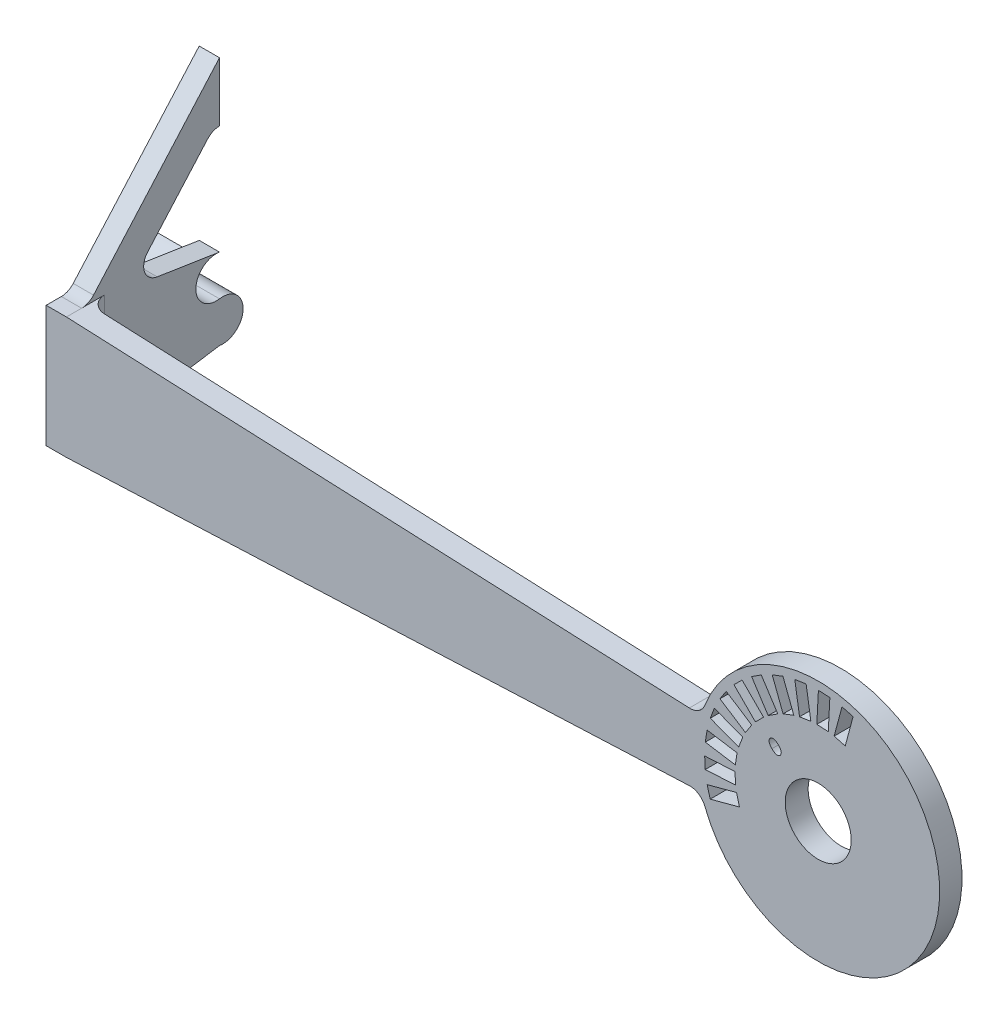
SolidWorks part; units mm, degrees
ref_plane "Front Plane" through (0, 0, 0) normal (0, 0, 1) x (1, 0, 0)
ref_plane "Top Plane" through (0, 0, 0) normal (0, 1, 0) x (1, 0, 0)
ref_plane "Right Plane" through (0, 0, 0) normal (1, 0, 0) x (0, 0, -1)
sketch "Sketch1" plane through (0, 0, 0) normal (0, 0, 1) x (1, 0, 0)
  circle A1 centre (27.25, 7.75) radius 5 construction
  circle A2 centre (27.25, 7.75) radius 9.525
  circle A3 centre (27.25, 7.75) radius 5.175
  dimension "D1" = 19.05
  dimension "D5" = 10
  dimension "D3" = 7.75
  dimension "D4" = 27.25
  dimension "D2" = 0.175
extrude "Boss-Extrude1" add sketch "Sketch1" against normal blind 3.6
sketch "Sketch2" plane through (0, 0, 0) normal (0, 0, 1) x (1, 0, 0)
  line L0 (18.995, 12.5019) -> (-90.625, 17.288)
  line L1 (18.995, 2.9981) -> (-90.625, -1.788)
  line L2 (18.995, 12.5019) -> (18.995, 2.9981)
  line L3 (-90.625, 17.288) -> (-90.625, -1.788)
  circle A0 centre (27.25, 7.75) radius 9.525 construction
  circle A1 centre (27.25, 7.75) radius 5.175 construction
  dimension "D1" = 87.5
  dimension "D2" = 87.5
  dimension "D3" = 8.255
  dimension "D4" = 109.62
extrude "Boss-Extrude2" add sketch "Sketch2" against normal blind 3.5
sketch "Sketch3" plane through (0, 0, 0) normal (0, 0, 1) x (1, 0, 0)
  circle A0 centre (27.25, 7.75) radius 19.05
  circle A1 centre (27.25, 7.75) radius 5.175 construction
  circle A2 centre (27.25, 7.75) radius 5.175
  dimension "D1" = 38.1
extrude "Boss-Extrude3" add sketch "Sketch3" against normal blind 3.5
sketch "Sketch4" plane through (0, 0, 0) normal (0, 0, 1) x (1, 0, 0)
  line L2 (27.25, 7.75) -> (20.4231, 25.5347) construction
  line L3 (27.25, 7.75) -> (24.2699, 26.5655) construction
  line L4 (27.25, 7.75) -> (28.247, 26.7739) construction
  line L5 (27.25, 7.75) -> (32.1805, 26.1509) construction
  line L6 (27.25, 7.75) -> (29.4192, 5.5808) construction
  line L12 (27.25, 7.75) -> (8.8491, 2.8195) construction
  line L13 (27.25, 7.75) -> (8.2261, 6.753) construction
  line L14 (27.25, 7.75) -> (8.4345, 10.7301) construction
  line L15 (27.25, 7.75) -> (9.4653, 14.5769) construction
  line L16 (27.25, 7.75) -> (11.2733, 18.1254) construction
  line L17 (13.7796, 21.2204) -> (11.2733, 18.1254) construction
  line L19 (13.7796, 21.2204) -> (16.8746, 23.7267) construction
  line L20 (16.8746, 23.7267) -> (20.4231, 25.5347) construction
  line L21 (20.4231, 25.5347) -> (24.2699, 26.5655) construction
  line L22 (24.2699, 26.5655) -> (28.247, 26.7739) construction
  line L23 (28.247, 26.7739) -> (32.1805, 26.1509) construction
  line L25 (8.2261, 6.753) -> (8.8491, 2.8195) construction
  line L26 (8.4345, 10.7301) -> (8.2261, 6.753) construction
  line L27 (9.4653, 14.5769) -> (8.4345, 10.7301) construction
  line L28 (11.2733, 18.1254) -> (9.4653, 14.5769) construction
  line L29 (19.4054, 18.1772) -> (16.8115, 22.1714)
  line L30 (17.4088, 16.3184) -> (18.6816, 17.5912)
  line L31 (17.4088, 16.3184) -> (14.0412, 19.686)
  line L32 (14.0412, 19.686) -> (15.314, 20.9588)
  line L33 (18.6816, 17.5912) -> (15.314, 20.9588)
  line L34 (14.6776, 20.3224) -> (18.0452, 16.9548) construction
  line L35 (15.725, 18.0022) -> (16.9978, 19.275) construction
  line L36 (19.4054, 18.1772) -> (20.915, 19.1576)
  line L37 (20.915, 19.1576) -> (18.3211, 23.1517)
  line L38 (16.8115, 22.1714) -> (18.3211, 23.1517)
  line L39 (21.7447, 19.5804) -> (20.038, 24.0265)
  line L40 (21.7447, 19.5804) -> (23.4252, 20.2254)
  line L41 (23.4252, 20.2254) -> (21.7184, 24.6716)
  line L42 (20.038, 24.0265) -> (21.7184, 24.6716)
  line L43 (24.3247, 20.4664) -> (23.5797, 25.1703)
  line L44 (24.3247, 20.4664) -> (26.1025, 20.748)
  line L45 (26.1025, 20.748) -> (25.3575, 25.4519)
  line L46 (23.5797, 25.1703) -> (25.3575, 25.4519)
  line L47 (27.0325, 20.7968) -> (27.2818, 25.5527)
  line L48 (27.0325, 20.7968) -> (28.83, 20.7026)
  line L49 (28.83, 20.7026) -> (29.0793, 25.4585)
  line L50 (27.2818, 25.5527) -> (29.0793, 25.4585)
  line L51 (29.7498, 20.5569) -> (30.9825, 25.1571)
  line L52 (29.7498, 20.5569) -> (31.4885, 20.091)
  line L53 (31.4885, 20.091) -> (32.7211, 24.6912)
  line L54 (30.9825, 25.1571) -> (32.7211, 24.6912)
  line L61 (15.8424, 14.085) -> (11.8483, 16.6789)
  line L62 (15.8424, 14.085) -> (16.8228, 15.5946)
  line L63 (16.8228, 15.5946) -> (12.8286, 18.1885)
  line L64 (11.8483, 16.6789) -> (12.8286, 18.1885)
  line L65 (14.7746, 11.5748) -> (10.3284, 13.2816)
  line L66 (14.7746, 11.5748) -> (15.4196, 13.2553)
  line L67 (15.4196, 13.2553) -> (10.9735, 14.962)
  line L68 (10.3284, 13.2816) -> (10.9735, 14.962)
  line L69 (14.252, 8.8975) -> (9.5481, 9.6425)
  line L70 (14.252, 8.8975) -> (14.5336, 10.6753)
  line L71 (14.5336, 10.6753) -> (9.8297, 11.4203)
  line L72 (9.5481, 9.6425) -> (9.8297, 11.4203)
  line L73 (14.2974, 6.17) -> (9.5415, 5.9207)
  line L74 (14.2974, 6.17) -> (14.2032, 7.9675)
  line L75 (14.2032, 7.9675) -> (9.4473, 7.7182)
  line L76 (9.5415, 5.9207) -> (9.4473, 7.7182)
  line L77 (14.909, 3.5115) -> (10.3088, 2.2789)
  line L78 (14.909, 3.5115) -> (14.4431, 5.2502)
  line L79 (14.4431, 5.2502) -> (9.8429, 4.0175)
  line L80 (10.3088, 2.2789) -> (9.8429, 4.0175)
  line L87 (15.2427, 2.6421) -> (10.9993, 0.48) [skipped]
  line L88 (16.0599, 1.0383) -> (15.2427, 2.6421) [skipped]
  line L89 (16.0599, 1.0383) -> (11.8165, -1.1239) [skipped]
  line L90 (11.8165, -1.1239) -> (10.9993, 0.48) [skipped]
  line L91 (33.9617, 18.9401) -> (36.1239, 23.1835) [skipped]
  line L92 (34.52, 24.0007) -> (36.1239, 23.1835) [skipped]
  line L93 (32.3579, 19.7573) -> (34.52, 24.0007) [skipped]
  line L94 (32.3579, 19.7573) -> (33.9617, 18.9401) [skipped]
  text T0 "\r\n0" font "Century Gothic" height in points 8
  point P23 (16.3614, 18.6386)
  dimension "D5" = 7
  dimension "D7" = 7
extrude "Cut-Extrude1" cut sketch "Sketch4" against normal through all
sketch "Sketch5" plane through (-90.625, 0, 0) normal (-1, 0, 0) x (0, 0, 1)
  line L0 (-24, 7.75) -> (0, 7.75) construction
  line L1 (0, 17.288) -> (0, -1.788) construction
  line L2 (-3.5, 17.275) -> (-3.5, -1.775) construction
  line L3 (0, 17.288) -> (-3.5, 17.288)
  line L4 (-3.5, 17.288) -> (-24, 14.1)
  line L5 (-24, 1.4) -> (-3.5, -1.788)
  line L6 (-3.5, -1.788) -> (0, -1.788)
  line L7 (0, -1.788) -> (0, 17.288)
  circle A0 centre (-24, 7.75) radius 6.35
  arc A1 (-24, 14.1) -> (-24, 7.75) centre (-23.5062, 10.925) cw
  arc A2 (-24, 7.75) -> (-24, 1.4) centre (-24.4938, 4.575) ccw
  dimension "D2" = 12.7
  dimension "D1" = 20.5
extrude "Boss-Extrude4" add sketch "Sketch5" along normal blind 3.175 contours A2 L5 L6 L7 L3 L4 A1
sketch "Sketch6" plane through (-93.8, 0, 0) normal (-1, 0, 0) x (0, 0, 1)
  circle A0 centre (-24, 7.75) radius 6.35
  arc A1 (-24, 7.75) -> (-24, 1.4) centre (-24.4938, 4.575) ccw construction
  arc A2 (-24, 7.75) -> (-24, 14.1) centre (-23.5062, 10.925) ccw construction
  arc A3 (-24, 7.75) -> (-24, 1.4) centre (-24.4938, 4.575) ccw
  arc A4 (-24, 7.75) -> (-24, 14.1) centre (-23.5062, 10.925) ccw
  arc M2 (-24, 14.1) -> (-24, 7.75) centre (-23.5062, 10.925) cw
  arc M3 (-24, 7.75) -> (-24, 1.4) centre (-24.4938, 4.575) ccw
  dimension "D1" = 12.7
extrude "Boss-Extrude5" add sketch "Sketch6" along normal blind 6.35 contours A0 M3 M2
sketch "Sketch7" [suppressed] plane through (0, 0, 0) normal (0, 0, 1) x (1, 0, 0)
  line L0 (27.25, 7.75) -> (36.775, 7.75) construction
  line L1 (33.7154, 7.0147) -> (33.4555, 5.792)
  line L2 (34.362, 8.375) -> (35.124, 8.375)
  line L3 (33.727, 7.74) -> (33.727, 7.76)
  line L4 (34.362, 7.125) -> (35.124, 7.125)
  line L5 (35.759, 7.74) -> (35.759, 7.76)
  line L6 (34.743, 7.125) -> (34.743, 8.375) construction
  line L7 (33.727, 7.75) -> (35.759, 7.75) construction
  line L8 (33.7154, 7.0147) -> (35.703, 6.5922)
  line L9 (35.703, 6.5922) -> (35.4431, 5.3695)
  line L10 (33.4555, 5.792) -> (35.4431, 5.3695)
  line L11 (27.25, 7.75) -> (36.5669, 5.7696) construction
  line L12 (33.4212, 5.6865) -> (32.9128, 4.5446)
  line L13 (33.4212, 5.6865) -> (35.2776, 4.86)
  line L14 (35.2776, 4.86) -> (34.7691, 3.7181)
  line L15 (32.9128, 4.5446) -> (34.7691, 3.7181)
  line L16 (27.25, 7.75) -> (35.9515, 3.8758) construction
  line L17 (32.8574, 4.4486) -> (32.1226, 3.4373)
  line L18 (32.8574, 4.4486) -> (34.5013, 3.2542)
  line L19 (34.5013, 3.2542) -> (33.7666, 2.2429)
  line L20 (32.1226, 3.4373) -> (33.7666, 2.2429)
  line L21 (27.25, 7.75) -> (34.9559, 2.1513) construction
  line L22 (32.0484, 3.3549) -> (31.1195, 2.5184)
  line L23 (32.0484, 3.3549) -> (33.4081, 1.8448)
  line L24 (33.4081, 1.8448) -> (32.4792, 1.0084)
  line L25 (31.1195, 2.5184) -> (32.4792, 1.0084)
  line L26 (27.25, 7.75) -> (33.6235, 0.6715) construction
  line L27 (31.0298, 2.4533) -> (29.9472, 1.8283)
  line L28 (31.0298, 2.4533) -> (32.0458, 0.6935)
  line L29 (32.0458, 0.6935) -> (30.9632, 0.0685)
  line L30 (29.9472, 1.8283) -> (30.9632, 0.0685)
  line L31 (27.25, 7.75) -> (32.0125, -0.4989) construction
  line L32 (29.8459, 1.7831) -> (28.6571, 1.3969)
  line L33 (29.8459, 1.7831) -> (30.4738, -0.1494)
  line L34 (30.4738, -0.1494) -> (29.285, -0.5357)
  line L35 (28.6571, 1.3969) -> (29.285, -0.5357)
  line L36 (27.25, 7.75) -> (30.1934, -1.3088) construction
  line L37 (27.25, 7.75) -> (33.727, 7.125) construction
  line L38 (27.25, 7.75) -> (33.4555, 5.792) construction
  line L39 (33.4555, 9.708) -> (33.7154, 8.4853)
  line L40 (33.4555, 9.708) -> (35.4431, 10.1305)
  line L41 (35.4431, 10.1305) -> (35.703, 8.9078)
  line L42 (33.7154, 8.4853) -> (35.703, 8.9078)
  line L43 (27.25, 7.75) -> (36.5669, 9.7304) construction
  line L44 (32.9128, 10.9554) -> (33.4212, 9.8135)
  line L45 (32.9128, 10.9554) -> (34.7691, 11.7819)
  line L46 (34.7691, 11.7819) -> (35.2776, 10.64)
  line L47 (33.4212, 9.8135) -> (35.2776, 10.64)
  line L48 (27.25, 7.75) -> (35.9515, 11.6242) construction
  line L49 (32.1226, 12.0627) -> (32.8574, 11.0514)
  line L50 (32.1226, 12.0627) -> (33.7666, 13.2571)
  line L51 (33.7666, 13.2571) -> (34.5013, 12.2458)
  line L52 (32.8574, 11.0514) -> (34.5013, 12.2458)
  line L53 (27.25, 7.75) -> (34.9559, 13.3487) construction
  line L54 (31.1195, 12.9816) -> (32.0484, 12.1451)
  line L55 (31.1195, 12.9816) -> (32.4792, 14.4916)
  line L56 (32.4792, 14.4916) -> (33.4081, 13.6552)
  line L57 (32.0484, 12.1451) -> (33.4081, 13.6552)
  line L58 (27.25, 7.75) -> (33.6235, 14.8285) construction
  line L59 (29.9472, 13.6717) -> (31.0298, 13.0467)
  line L60 (29.9472, 13.6717) -> (30.9632, 15.4315)
  line L61 (30.9632, 15.4315) -> (32.0458, 14.8065)
  line L62 (31.0298, 13.0467) -> (32.0458, 14.8065)
  line L63 (27.25, 7.75) -> (32.0125, 15.9989) construction
  line L64 (28.6571, 14.1031) -> (29.8459, 13.7169)
  line L65 (28.6571, 14.1031) -> (29.285, 16.0357)
  line L66 (29.285, 16.0357) -> (30.4738, 15.6494)
  line L67 (29.8459, 13.7169) -> (30.4738, 15.6494)
  line L68 (27.25, 7.75) -> (30.1934, 16.8088) construction
  line L69 (27.25, 7.75) -> (33.727, 8.375) construction
  line L70 (27.25, 7.75) -> (33.4555, 9.708) construction
  arc A0 (18.995, 2.9981) -> (18.995, 12.5019) centre (27.25, 7.75) ccw construction
  circle A1 centre (27.25, 7.75) radius 5.125 construction
  arc A2 (34.362, 8.375) -> (33.727, 7.74) centre (34.362, 7.74) ccw
  arc A3 (33.727, 7.76) -> (34.362, 7.125) centre (34.362, 7.76) ccw
  arc A4 (35.124, 7.125) -> (35.759, 7.76) centre (35.124, 7.76) ccw
  arc A5 (35.124, 8.375) -> (35.759, 7.74) centre (35.124, 7.74) cw
  point P6 (34.743, 7.75)
  point P12 (33.727, 8.375)
  point P83 (33.727, 7.125)
  point P86 (35.759, 7.125)
  point P89 (35.759, 8.375)
  dimension "D8" = 0.635
  dimension "D1" = 2.032
  dimension "D2" = 1.25
  dimension "D3" = 1.016
  dimension "D5" = 12
  dimension "D7" = 12
  dimension "D4" = 7
  dimension "D6" = 7
extrude "Cut-Extrude2" [suppressed] cut sketch "Sketch7" against normal through all contours L64 L67 L66 L65 | L59 L62 L61 L60 | L54 L57 L56 L55 | L49 L52 L51 L50 | L44 L47 L46 L45 | L39 L42 L41 L40 | A5 L2 A2 A3 L4 A4 | L12 L15 L14 L13 | L22 L25 L24 L23 | L27 L30 L29 L28 | L32 L35 L34 L33 | L17 L20 L19 L18 | L1 L10 L9 L8
sketch "Sketch8" [suppressed] plane through (0, 0, 0) normal (0, 0, 1) x (1, 0, 0)
  line L0 (27.25, 7.75) -> (38.5, 7.75) construction
  line L1 (35.7484, 8.2182) -> (38.5, 9.25)
  line L2 (38.5, 9.25) -> (38.5, 6.25)
  line L3 (38.5, 6.25) -> (35.7484, 7.2818)
  line L4 (38.566, 8.6218) -> (34.3416, 9.2574)
  line L5 (34.3416, 9.2574) -> (37.9423, 11.5562)
  line L6 (37.9423, 11.5562) -> (38.566, 8.6218)
  line L7 (27.25, 7.75) -> (38.2542, 10.089) construction
  line L8 (38.1375, 10.9555) -> (33.8732, 10.6988)
  line L9 (33.8732, 10.6988) -> (36.9173, 13.6961)
  line L10 (36.9173, 13.6961) -> (38.1375, 10.9555)
  line L11 (27.25, 7.75) -> (37.5274, 12.3258) construction
  line L12 (37.2331, 13.1491) -> (33.1154, 12.0114)
  line L13 (33.1154, 12.0114) -> (35.4698, 15.5761)
  line L14 (35.4698, 15.5761) -> (37.2331, 13.1491)
  line L15 (27.25, 7.75) -> (36.3514, 14.3626) construction
  line L16 (35.8924, 15.1067) -> (32.1012, 13.1378)
  line L17 (32.1012, 13.1378) -> (33.663, 17.1141)
  line L18 (33.663, 17.1141) -> (35.8924, 15.1067)
  line L19 (27.25, 7.75) -> (34.7777, 16.1104) construction
  line L20 (34.174, 16.7428) -> (30.875, 14.0287)
  line L21 (30.875, 14.0287) -> (31.576, 18.2428)
  line L22 (31.576, 18.2428) -> (34.174, 16.7428)
  line L23 (27.25, 7.75) -> (32.875, 17.4928) construction
  line L24 (32.153, 17.9859) -> (29.4904, 14.6452)
  line L25 (29.4904, 14.6452) -> (29.2999, 18.9129)
  line L26 (29.2999, 18.9129) -> (32.153, 17.9859)
  line L27 (27.25, 7.75) -> (30.7264, 18.4494) construction
  line L28 (27.25, 7.75) -> (34.5, 7.75) construction
  line L29 (27.25, 7.75) -> (34.3416, 9.2574) construction
  line L30 (37.9423, 3.9438) -> (34.3416, 6.2426)
  line L31 (34.3416, 6.2426) -> (38.566, 6.8782)
  line L32 (38.566, 6.8782) -> (37.9423, 3.9438)
  line L33 (27.25, 7.75) -> (38.2542, 5.411) construction
  line L34 (36.9173, 1.8039) -> (33.8732, 4.8012)
  line L35 (33.8732, 4.8012) -> (38.1375, 4.5445)
  line L36 (38.1375, 4.5445) -> (36.9173, 1.8039)
  line L37 (27.25, 7.75) -> (37.5274, 3.1742) construction
  line L38 (35.4698, -0.0761) -> (33.1154, 3.4886)
  line L39 (33.1154, 3.4886) -> (37.2331, 2.3509)
  line L40 (37.2331, 2.3509) -> (35.4698, -0.0761)
  line L41 (27.25, 7.75) -> (36.3514, 1.1374) construction
  line L42 (33.663, -1.6141) -> (32.1012, 2.3622)
  line L43 (32.1012, 2.3622) -> (35.8924, 0.3933)
  line L44 (35.8924, 0.3933) -> (33.663, -1.6141)
  line L45 (27.25, 7.75) -> (34.7777, -0.6104) construction
  line L46 (31.576, -2.7428) -> (30.875, 1.4713)
  line L47 (30.875, 1.4713) -> (34.174, -1.2428)
  line L48 (34.174, -1.2428) -> (31.576, -2.7428)
  line L49 (27.25, 7.75) -> (32.875, -1.9928) construction
  line L50 (29.2999, -3.4129) -> (29.4904, 0.8548)
  line L51 (29.4904, 0.8548) -> (32.153, -2.4859)
  line L52 (32.153, -2.4859) -> (29.2999, -3.4129)
  line L53 (27.25, 7.75) -> (30.7264, -2.9494) construction
  line L54 (27.25, 7.75) -> (34.5, 7.75) construction
  line L55 (27.25, 7.75) -> (34.3416, 6.2426) construction
  circle A0 centre (27.25, 7.75) radius 5.125 construction
  arc A1 (35.7484, 8.2182) -> (35.7484, 7.2818) centre (35.924, 7.75) ccw
  point P65 (34.5, 7.75)
  dimension "D8" = 0.5
  dimension "D1" = 4
  dimension "D2" = 3
  dimension "D3" = 7.25
  dimension "D5" = 12
  dimension "D7" = 12
  dimension "D4" = 7
  dimension "D6" = 7
extrude "Cut-Extrude3" [suppressed] cut sketch "Sketch8" against normal through all
sketch "Sketch9" plane through (-90.625, 0, 0) normal (1, 0, 0) x (0, 0, -1)
  line L0 (3.5, 17.288) -> (24, 40.4922)
  line L1 (24, 32.4922) -> (24, 31.2163)
  line L2 (3.5, 17.288) -> (24, 14.1) construction
  line L3 (24, 40.4922) -> (24, 32.4922)
  line L4 (24, 32.4922) -> (9.714, 16.3217)
  line L5 (9.714, 16.3217) -> (3.5, 17.288)
  line L6 (3.5, 17.288) -> (3.5, -1.788) construction
  line L7 (22.1264, 30.3715) -> (25.8736, 30.3715) construction
  line L8 (24, 31.2163) -> (24, 30.3715) construction
  line L9 (24, 32.4922) -> (25.7625, 30.3715) construction
  arc A0 (22.1264, 30.3715) -> (24, 31.2163) centre (24, 28.7163) cw
  arc A1 (24, 31.2163) -> (25.8736, 30.3715) centre (24, 28.7163) cw construction
  line M5 (24, 14.1) -> (3.5, 17.288)
  dimension "D3" = 2.5
  dimension "D5" = 2.5
  dimension "D1" = 8
  dimension "D2" = 32.7422
  dimension "D4" = 39.73
extrude "Boss-Extrude6" add sketch "Sketch9" against normal blind 3.18 contours L4 L3 L0 M5 | L4 A0 L1
sketch "Sketch10" plane through (-90.625, 0, 0) normal (1, 0, 0) x (0, 0, -1)
  line L0 (3.5, -1.788) -> (24, -24.9922)
  line L1 (24, -16.9922) -> (24, -15.7163)
  line L2 (24, 1.4) -> (3.5, -1.788) construction
  line L3 (24, -24.9922) -> (24, -16.9922)
  line L4 (24, -16.9922) -> (9.714, -0.8217)
  line L5 (9.714, -0.8217) -> (3.5, -1.788)
  line L6 (25.8736, -14.8715) -> (22.1264, -14.8715) construction
  line L7 (24, -15.7163) -> (24, -14.8715) construction
  arc A0 (22.1264, -14.8715) -> (24, -15.7163) centre (24, -13.2163) ccw
  arc A1 (24, -15.7163) -> (25.8736, -14.8715) centre (24, -13.2163) ccw construction
  line M7 (3.5, -1.788) -> (24, 1.4)
  dimension "D3" = 2.5
  dimension "D4" = 2.5
  dimension "D1" = 8
  dimension "D2" = 32.7422
extrude "Boss-Extrude7" [suppressed] add sketch "Sketch10" against normal blind 3.18 contours L3 L4 L0 M7 | A0 L4 L1
fillet "Fillet1" radius 2.5 5 edges at (8.9211, 2.5583, -1.75) (8.9211, 12.9417, -1.75) (-90.625, 7.75, -3.5) (-92.2125, 16.3217, -9.714) (-92.2125, 17.288, -3.5)
fillet "Fillet2" [suppressed] radius 2.5
